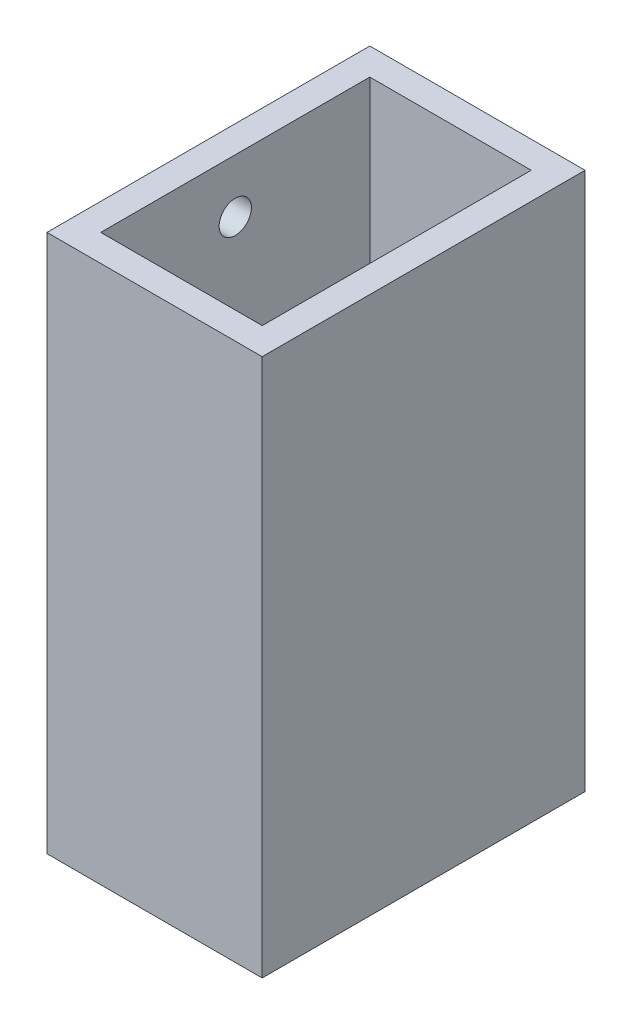
SolidWorks part; units mm, degrees
material "ABS"
ref_plane "Front Plane" through (0, 0, 0) normal (0, 0, 1) x (1, 0, 0)
ref_plane "Top Plane" through (0, 0, 0) normal (0, 1, 0) x (1, 0, 0)
ref_plane "Right Plane" through (0, 0, 0) normal (1, 0, 0) x (0, 0, -1)
sketch "Sketch2" plane through (0, 0, 0) normal (0, 1, 0) x (1, 0, 0)
  line L0 (0, 0) -> (-40, 0)
  line L1 (0, 0) -> (0, -60)
  line L2 (-40, 0) -> (-40, -60)
  line L3 (0, -60) -> (-40, -60)
  dimension "D1" = 40
  dimension "D2" = 60
extrude "Boss-Extrude1" add sketch "Sketch2" along normal blind 100
sketch "Sketch3" plane through (-40, 0, 0) normal (-1, 0, 0) x (0, 0, 1)
  line L0 (30, 100) -> (30, 90) construction
  line L1 (0, 100) -> (60, 100) construction
  circle A0 centre (30, 90) radius 3
  dimension "D2" = 6
  dimension "D1" = 10
shell "Shell1" thickness 5 removed face at (-20, 0, 30) removed face at (-20, 100, 30)
extrude "Cut-Extrude1" cut sketch "Sketch3" against normal blind 10
